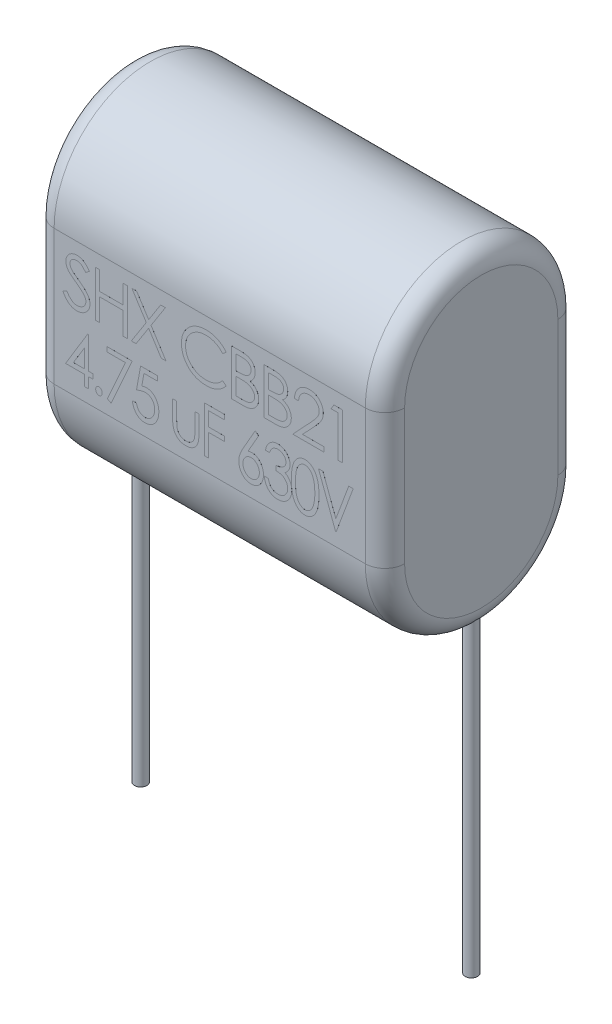
SolidWorks part; units mm, degrees
ref_plane "Front Plane" through (0, 0, 0) normal (0, 0, 1) x (1, 0, 0)
ref_plane "Top Plane" through (0, 0, 0) normal (0, 1, 0) x (1, 0, 0)
ref_plane "Right Plane" through (0, 0, 0) normal (1, 0, 0) x (0, 0, -1)
sketch "Sketch1" plane through (0, 0, 0) normal (1, 0, 0) x (0, 0, -1)
  line L0 (0, 5.15) -> (0, -5.15) construction
  line L1 (7.35, 5.15) -> (7.35, -5.15)
  line L2 (-7.35, 5.15) -> (-7.35, -5.15)
  line L3 (0, 12.5) -> (9.814, 12.5) construction
  line L4 (0, -12.5) -> (9.814, -12.5) construction
  arc A0 (7.35, 5.15) -> (-7.35, 5.15) centre (0, 5.15) ccw
  arc A1 (-7.35, -5.15) -> (7.35, -5.15) centre (0, -5.15) ccw
  point P3 (0, 0)
  dimension "D1" = 25
  dimension "D2" = 14.7
extrude "Boss-Extrude1" add sketch "Sketch1" along normal mid plane 26.75
fillet "Fillet1" radius 1.5 8 edges at (-13.375, 0, 7.35) (-13.375, -12.5, 0) (-13.375, 0, -7.35) (-13.375, 12.5, 0) (13.375, 0, -7.35) (13.375, -12.5, 0) (13.375, 0, 7.35) (13.375, 12.5, 0)
sketch "Sketch2" plane through (0, 0, 0) normal (0, 1, 0) x (1, 0, 0)
  line L0 (0, 0) -> (0, 5.286) construction
  line L1 (0, 0) -> (-7.4166, 0) construction
  line L2 (-12.15, 0) -> (-12.15, -1.5103) construction
  circle A0 centre (-12.62, 0) radius 0.47
  circle A1 centre (12.62, 0) radius 0.47
  point P8 (-12.6218, -0.0809)
  point P9 (0, 0)
  dimension "D1" = 12.15
  dimension "D2" = 0.94
extrude "Boss-Extrude3" add sketch "Sketch2" against normal blind 35.5
sketch "Sketch3" plane through (0, 0, 0) normal (0, 0, 1) x (1, 0, 0)
  line L0 (-11.875, 0.65) -> (11.875, 0.65) construction
  line L1 (-11.875, 5.15) -> (-11.875, -5.15) construction
  line L2 (11.875, -5.15) -> (11.875, 5.15) construction
  line L3 (-11.875, -4.15) -> (11.875, -4.15) construction
  line L4 (11.875, 5.15) -> (-11.875, 5.15) construction
  text T0 "SHX CBB21" font "Century Gothic" height 3.5
  text T1 "4.75 uF 630V" font "Century Gothic" height 3.5
  dimension "D1" = 4.5
  dimension "D2" = 4.8
extrude "Boss-Extrude4" add sketch "Sketch3" along normal blind 0.001 from surface starting at face at (0, 0, 7.35)
